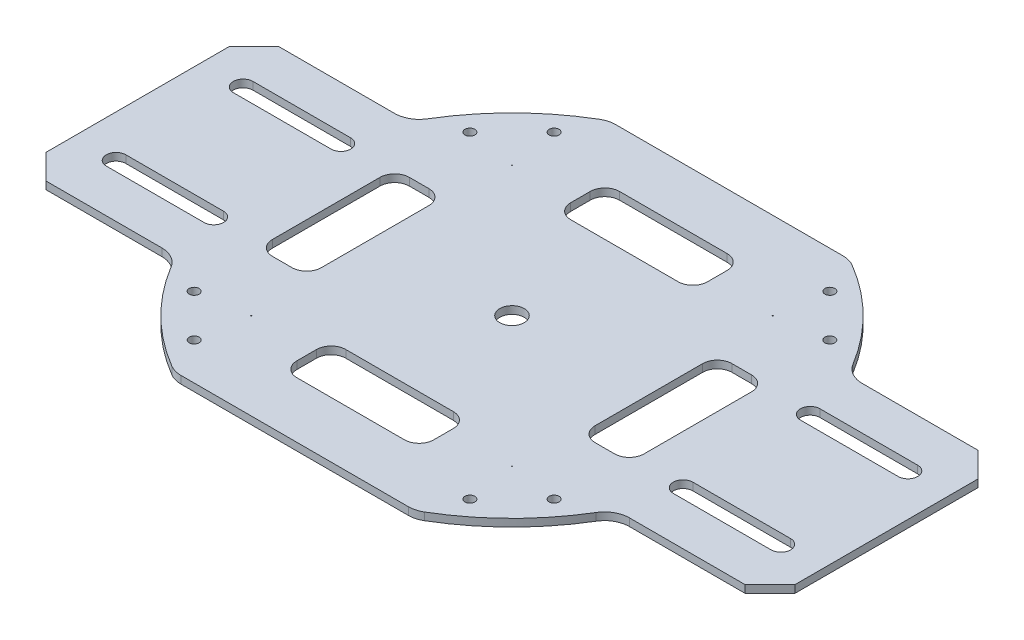
SolidWorks part; units mm, degrees
ref_plane "Front Plane" through (0, 0, 0) normal (0, 0, 1) x (1, 0, 0)
ref_plane "Top Plane" through (0, 0, 0) normal (0, 1, 0) x (1, 0, 0)
ref_plane "Right Plane" through (0, 0, 0) normal (1, 0, 0) x (0, 0, -1)
sketch "Sketch1" plane through (0, 0, 0) normal (0, 1, 0) x (1, 0, 0)
  line L0 (0, -1000) -> (0, 49000) construction
  line L1 (-23.2448, 44.45) -> (23.2448, 44.45)
  line L2 (-76.5969, 18.7325) -> (-76.5969, -18.7325)
  line L3 (-23.2448, -44.45) -> (23.2448, -44.45)
  line L4 (76.5969, 18.7325) -> (76.5969, -18.7325)
  line L6 (35.4178, 36.4243) -> (41.9684, 29.8736) construction
  line L7 (-76.5969, 0) -> (76.5969, 0) construction
  line L8 (-71.5169, 23.8125) -> (-47.8309, 23.8125)
  line L9 (-71.5169, -23.8125) -> (-47.8309, -23.8125)
  line L10 (-23.8125, 64.7529) -> (-23.8125, -44.45) construction
  line L11 (23.8125, 64.7529) -> (23.8125, -44.45) construction
  line L12 (47.8309, -23.8125) -> (71.5169, -23.8125)
  line L13 (47.8309, 23.8125) -> (71.5169, 23.8125)
  line L14 (-76.5969, -18.7325) -> (-71.5169, -23.8125)
  line L15 (-71.5169, 23.8125) -> (-76.5969, 18.7325)
  line L16 (71.5169, 23.8125) -> (76.5969, 18.7325)
  line L17 (71.5169, -23.8125) -> (76.5969, -18.7325)
  line L18 (707.1068, -707.1068) -> (-34648.2323, 34648.2323) construction
  line L19 (-707.1068, -707.1068) -> (34648.2323, 34648.2323) construction
  circle A0 centre (0, 0) radius 2.5
  arc A1 (-25.8276, 43.7444) -> (-43.4827, 26.2659) centre (0, 0) ccw
  arc A2 (25.8276, 43.7444) -> (23.2448, 44.45) centre (23.2448, 39.37) ccw
  arc A3 (-23.2448, 44.45) -> (-25.8276, 43.7444) centre (-23.2448, 39.37) ccw
  arc A4 (25.8276, -43.7444) -> (43.4827, -26.2659) centre (0, 0) ccw
  arc A5 (25.8276, -43.7444) -> (23.2448, -44.45) centre (23.2448, -39.37) cw
  arc A6 (-25.8276, -43.7444) -> (-23.2448, -44.45) centre (-23.2448, -39.37) ccw
  arc A7 (-43.4827, -26.2659) -> (-25.8276, -43.7444) centre (0, 0) ccw
  arc A8 (43.4827, 26.2659) -> (25.8276, 43.7444) centre (0, 0) ccw
  arc A9 (-47.8309, -23.8125) -> (-43.4827, -26.2659) centre (-47.8309, -28.8925) cw
  arc A10 (47.8309, -23.8125) -> (43.4827, -26.2659) centre (47.8309, -28.8925) ccw
  arc A11 (43.4827, 26.2659) -> (47.8309, 23.8125) centre (47.8309, 28.8925) ccw
  arc A12 (-47.8309, 23.8125) -> (-43.4827, 26.2659) centre (-47.8309, 28.8925) ccw
  circle A13 centre (36.8191, 28.198) radius 1.016
  circle A14 centre (28.198, 36.8191) radius 1.016
  circle A15 centre (26.6716, 26.6716) radius 0.081
  circle A16 centre (26.6716, -26.6716) radius 0.081
  circle A17 centre (36.8191, -28.198) radius 1.016
  circle A18 centre (28.198, -36.8191) radius 1.016
  circle A19 centre (-26.6716, -26.6716) radius 0.081
  circle A20 centre (-28.198, -36.8191) radius 1.016
  circle A21 centre (-36.8191, -28.198) radius 1.016
  circle A22 centre (-26.6716, 26.6716) radius 0.081
  circle A23 centre (-36.8191, 28.198) radius 1.016
  circle A24 centre (-28.198, 36.8191) radius 1.016
  point P0 (0, 0)
  point P8 (76.5969, -23.8125)
  point P11 (-76.5969, -23.8125)
  point P12 (-76.5969, 23.8125)
  point P34 (76.5969, 23.8125)
  point P81 (0, 0)
  dimension "D3" = 5
  dimension "D6" = 5.08
  dimension "D1" = 5.08
  dimension "D2" = 5.08
  dimension "D7" = 4.826
  dimension "D4" = 23.8125
  dimension "D5" = 23.8125
  dimension "D8" = 6.096
  dimension "D13" = 4
extrude "Boss-Extrude1" add sketch "Sketch1" along normal blind 1.55
sketch "Sketch2" plane through (0, 1.55, 0) normal (0, 1, 0) x (1, 0, 0)
  line L0 (-76.5969, 0) -> (76.5969, 0) construction
  line L1 (-76.5969, 18.7325) -> (-76.5969, -18.7325) construction
  line L2 (76.5969, -18.7325) -> (76.5969, 18.7325) construction
  line L3 (48, 13) -> (68, 13) construction
  line L4 (48, 15) -> (68, 15)
  line L5 (48, 11) -> (68, 11)
  line L6 (48, -13) -> (68, -13) construction
  line L7 (48, -15) -> (68, -15)
  line L8 (48, -11) -> (68, -11)
  line L9 (0, 44.45) -> (0, -44.45) construction
  line L10 (23.2448, 44.45) -> (-23.2448, 44.45) construction
  line L11 (-23.2448, -44.45) -> (23.2448, -44.45) construction
  line L12 (-48, 13) -> (-68, 13) construction
  line L13 (-48, 15) -> (-68, 15)
  line L14 (-48, 11) -> (-68, 11)
  line L15 (-48, -13) -> (-68, -13) construction
  line L16 (-48, -15) -> (-68, -15)
  line L17 (-48, -11) -> (-68, -11)
  arc A0 (48, 15) -> (48, 11) centre (48, 13) ccw
  arc A1 (68, 11) -> (68, 15) centre (68, 13) ccw
  arc A2 (48, -15) -> (48, -11) centre (48, -13) cw
  arc A3 (68, -11) -> (68, -15) centre (68, -13) cw
  arc A4 (-48, 15) -> (-48, 11) centre (-48, 13) cw
  arc A5 (-68, 11) -> (-68, 15) centre (-68, 13) cw
  arc A6 (-48, -15) -> (-48, -11) centre (-48, -13) ccw
  arc A7 (-68, -11) -> (-68, -15) centre (-68, -13) ccw
  point P8 (58, 13)
  point P15 (58, -13)
  point P20 (46, 13)
  point P21 (70, 13)
  point P33 (-58, 13)
  point P40 (-58, -13)
  dimension "D1" = 11
  dimension "D2" = 15
  dimension "D4" = 46
  dimension "D5" = 70
extrude "Cut-Extrude1" cut sketch "Sketch2" against normal through all
sketch "Sketch3" plane through (0, 1.55, 0) normal (0, 1, 0) x (1, 0, 0)
  line L0 (-76.5969, 0) -> (76.5969, 0) construction
  line L1 (-11, 33) -> (11, 33)
  line L2 (-14, 30) -> (-14, 26)
  line L3 (-11, 23) -> (11, 23)
  line L4 (14, 30) -> (14, 26)
  line L5 (-76.5969, 18.7325) -> (-76.5969, -18.7325) construction
  line L6 (76.5969, -18.7325) -> (76.5969, 18.7325) construction
  line L7 (0, 44.45) -> (0, -44.45) construction
  line L8 (23.2448, 44.45) -> (-23.2448, 44.45) construction
  line L9 (-23.2448, -44.45) -> (23.2448, -44.45) construction
  line L10 (14, -30) -> (14, -26)
  line L11 (-11, -23) -> (11, -23)
  line L12 (-14, -30) -> (-14, -26)
  line L13 (-11, -33) -> (11, -33)
  line L14 (-28, -14) -> (-38, 14) construction
  line L15 (31, 14) -> (35, 14)
  line L16 (28, 11) -> (28, -11)
  line L17 (31, -14) -> (35, -14)
  line L18 (38, 11) -> (38, -11)
  line L19 (28, 14) -> (38, -14) construction
  line L20 (28, -14) -> (38, 14) construction
  line L21 (-28, 14) -> (-38, -14) construction
  line L22 (-38, 11) -> (-38, -11)
  line L23 (-31, -14) -> (-35, -14)
  line L24 (-28, 11) -> (-28, -11)
  line L25 (-31, 14) -> (-35, 14)
  arc A0 (-11, 33) -> (-14, 30) centre (-11, 30) ccw
  arc A1 (-14, 26) -> (-11, 23) centre (-11, 26) ccw
  arc A2 (11, 23) -> (14, 26) centre (11, 26) ccw
  arc A3 (11, 33) -> (14, 30) centre (11, 30) cw
  arc A4 (11, -33) -> (14, -30) centre (11, -30) ccw
  arc A5 (11, -23) -> (14, -26) centre (11, -26) cw
  arc A6 (-14, -26) -> (-11, -23) centre (-11, -26) cw
  arc A7 (-11, -33) -> (-14, -30) centre (-11, -30) cw
  arc A8 (35, -14) -> (38, -11) centre (35, -11) ccw
  arc A9 (28, -11) -> (31, -14) centre (31, -11) ccw
  arc A10 (31, 14) -> (28, 11) centre (31, 11) ccw
  arc A11 (35, 14) -> (38, 11) centre (35, 11) cw
  arc A12 (-35, 14) -> (-38, 11) centre (-35, 11) ccw
  arc A13 (-31, 14) -> (-28, 11) centre (-31, 11) cw
  arc A14 (-28, -11) -> (-31, -14) centre (-31, -11) cw
  arc A15 (-35, -14) -> (-38, -11) centre (-35, -11) cw
  point P36 (33, 0)
  point P69 (-33, 0)
  dimension "D5" = 3
  dimension "D9" = 3
  dimension "D1" = 23
  dimension "D2" = 33
  dimension "D3" = 28
  dimension "D4" = 14
  dimension "D6" = 28
  dimension "D7" = 38
  dimension "D8" = 28
extrude "Cut-Extrude2" cut sketch "Sketch3" against normal through all
